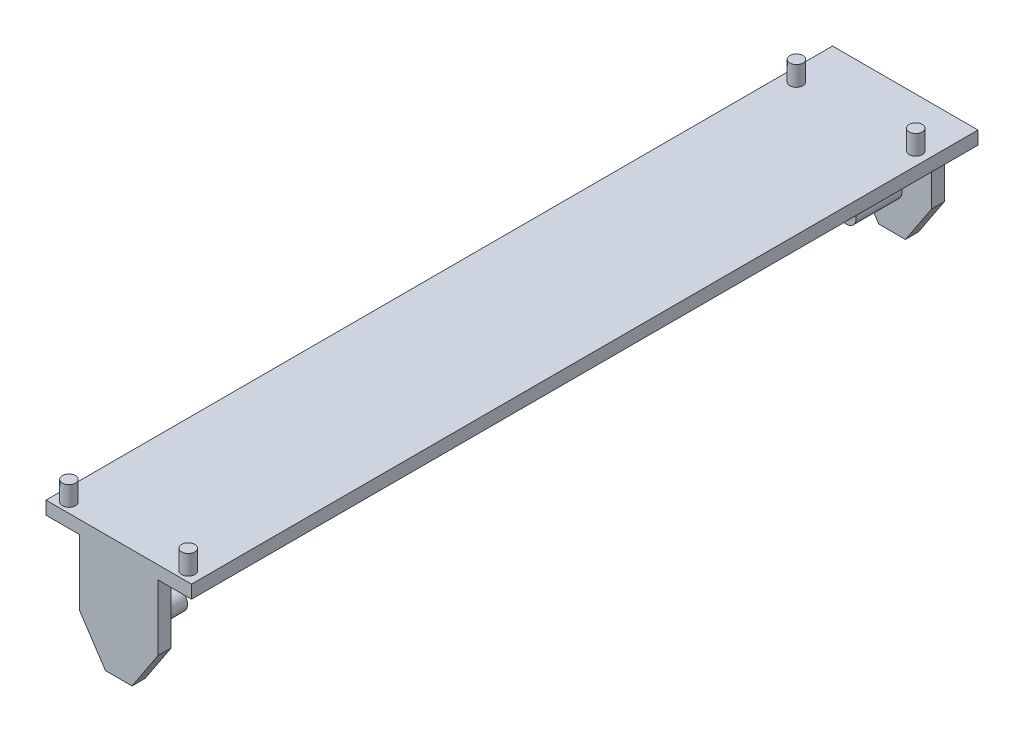
SolidWorks part; units mm, degrees
ref_plane "Front Plane" through (0, 0, 0) normal (0, 0, 1) x (1, 0, 0)
ref_plane "Top Plane" through (0, 0, 0) normal (0, 1, 0) x (1, 0, 0)
ref_plane "Right Plane" through (0, 0, 0) normal (1, 0, 0) x (0, 0, -1)
sketch "Sketch1" plane through (0, 0, 0) normal (0, 0, 1) x (1, 0, 0)
  line L3 (30, 0) -> (30, 50)
  line L4 (30, 50) -> (-30, 50)
  line L5 (-30, 50) -> (-30, 0)
  line L6 (-30, 0) -> (-10.1433, -30)
  line L7 (0, 0) -> (0, -30) construction
  line L8 (-10.1433, -30) -> (10.1433, -30)
  line L9 (30, 0) -> (10.1433, -30)
  circle A0 centre (0, 0) radius 7.5
  dimension "D1" = 60
  dimension "D6" = 15
  dimension "D7" = 30
  dimension "D2" = 30
  dimension "D3" = 50
  dimension "D4" = 0
  dimension "D5" = 50
extrude "Boss-Extrude1" add sketch "Sketch1" along normal blind 10 contours A0 | A0 L9 L3 L4 L5 L6 region at (0, 14.8759, 0) region at (0, 0, 0)
extrude "Boss-Extrude2" add sketch "Sketch1<3>" against normal blind 35 contours A0 region at (0, 0, 0)
sketch "Sketch1<3>" plane through (0, 0, 0) normal (0, 0, 1) x (1, 0, 0) same geometry as "Sketch1"
sketch "Sketch3" plane through (0, 0, 10) normal (0, 0, 1) x (1, 0, 0)
  line L1 (-55.5, 50) -> (55.5, 50)
  line L2 (-55.5, 50) -> (-55.5, 60)
  line L3 (-55.5, 60) -> (55.5, 60)
  line L4 (55.5, 50) -> (55.5, 60)
  line L6 (-30, 50) -> (-30, 0) construction
  line L7 (30, 50) -> (-30, 50) construction
  point P5 (-30, 50)
  point P6 (0, 0)
  point P9 (-43.6233, 59.6246)
  dimension "D1" = 10
  dimension "D2" = 111
  dimension "D3" = 10
  dimension "D4" = 25.5
  dimension "D5" = 0
extrude "Boss-Extrude3" add sketch "Sketch3" against normal blind 300
mirror "Mirror1" about plane through (0, 0, -290) normal (0, 0, -1) of "Boss-Extrude2", "Boss-Extrude3", "Boss-Extrude1"
sketch "Sketch4" plane through (0, 60, 0) normal (0, 1, 0) x (1, 0, 0)
  line L0 (-55.5, 590) -> (-55.5, -10) construction
  line L1 (55.5, 590) -> (55.5, -10) construction
  line L2 (55.5, -10) -> (-55.5, -10) construction
  circle A0 centre (-45.5, -2.5) radius 5
  circle A1 centre (45.5, -2.5) radius 5
  circle A2 centre (-45.5, 552.5) radius 5
  circle A3 centre (45.5, 552.5) radius 5
  dimension "D1" = 10
  dimension "D2" = 10
  dimension "D7" = 10
  dimension "D8" = 10
  dimension "D3" = 10
  dimension "D4" = 10
  dimension "D5" = 7.5
  dimension "D6" = 7.5
  dimension "D9" = 555
  dimension "D10" = 555
  dimension "D11" = 10
  dimension "D12" = 10
extrude "Boss-Extrude4" add sketch "Sketch4" along normal blind 15
